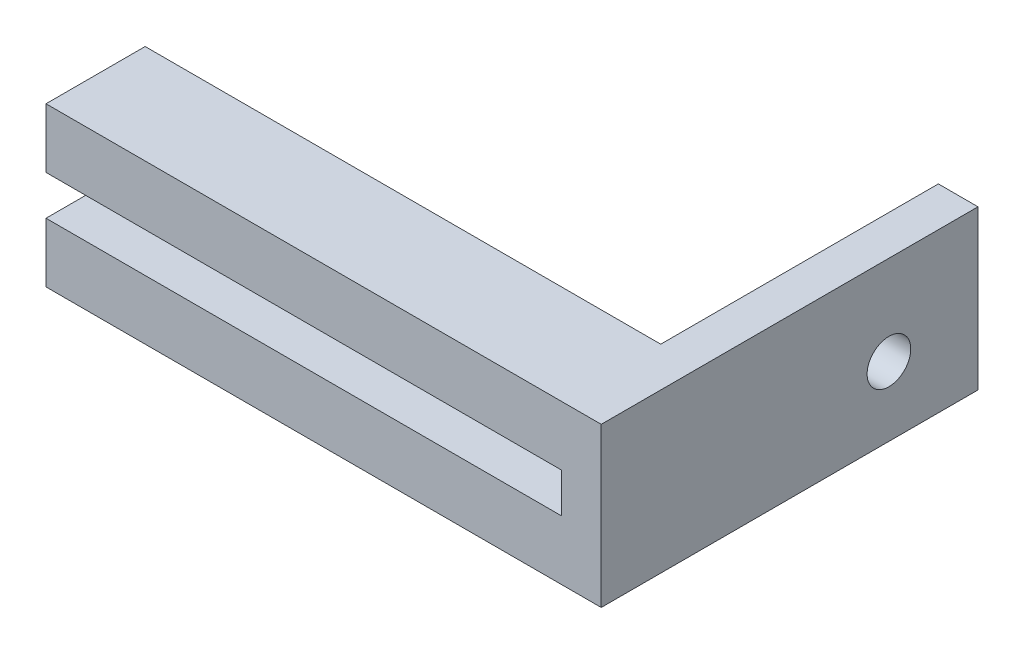
SolidWorks part; units mm, degrees
ref_plane "Front Plane" through (0, 0, 0) normal (0, 0, 1) x (1, 0, 0)
ref_plane "Top Plane" through (0, 0, 0) normal (0, 1, 0) x (1, 0, 0)
ref_plane "Right Plane" through (0, 0, 0) normal (1, 0, 0) x (0, 0, -1)
sketch "Sketch1" plane through (0, 0, 0) normal (1, 0, 0) x (0, 0, -1)
  line L1 (-35.9146, 20.1296) -> (59.0854, 20.1296)
  line L2 (-35.9146, 20.1296) -> (-35.9146, -19.8704)
  line L3 (-35.9146, -19.8704) -> (59.0854, -19.8704)
  line L4 (59.0854, 20.1296) -> (59.0854, -19.8704)
  dimension "D1" = 95
  dimension "D2" = 40
extrude "Boss-Extrude1" add sketch "Sketch1" along normal blind 10
sketch "Sketch4" plane through (0, 0, 0) normal (-1, 0, 0) x (0, 0, 1)
  line L0 (-59.0854, 20.1296) -> (35.9146, 20.1296) construction
  line L1 (10.9146, 20.1296) -> (35.9146, 20.1296)
  line L2 (10.9146, 20.1296) -> (10.9146, 5.1296)
  line L3 (10.9146, 5.1296) -> (35.9146, 5.1296)
  line L4 (35.9146, 20.1296) -> (35.9146, 5.1296)
  line L5 (35.9146, 20.1296) -> (35.9146, -19.8704) construction
  line L6 (35.9146, -19.8704) -> (-59.0854, -19.8704) construction
  line L7 (35.9146, -4.8704) -> (10.9146, -4.8704)
  line L8 (35.9146, -4.8704) -> (35.9146, -19.8704)
  line L9 (35.9146, -19.8704) -> (10.9146, -19.8704)
  line L10 (10.9146, -4.8704) -> (10.9146, -19.8704)
  dimension "D1" = 25
  dimension "D2" = 10
  dimension "D3" = 25
  dimension "D4" = 15
extrude "Boss-Extrude4" add sketch "Sketch4" along normal blind 130
sketch "Sketch5" plane through (0, 0, 0) normal (-1, 0, 0) x (0, 0, 1)
  line L0 (10.9146, -19.8704) -> (-59.0854, -19.8704) construction
  line L1 (-59.0854, -19.8704) -> (-59.0854, 20.1296) construction
  circle A0 centre (-36.6254, -2.4304) radius 5.5
  dimension "D1" = 11
  dimension "D2" = 17.44
  dimension "D3" = 22.46
extrude "Cut-Extrude1" cut sketch "Sketch5" against normal blind 27
